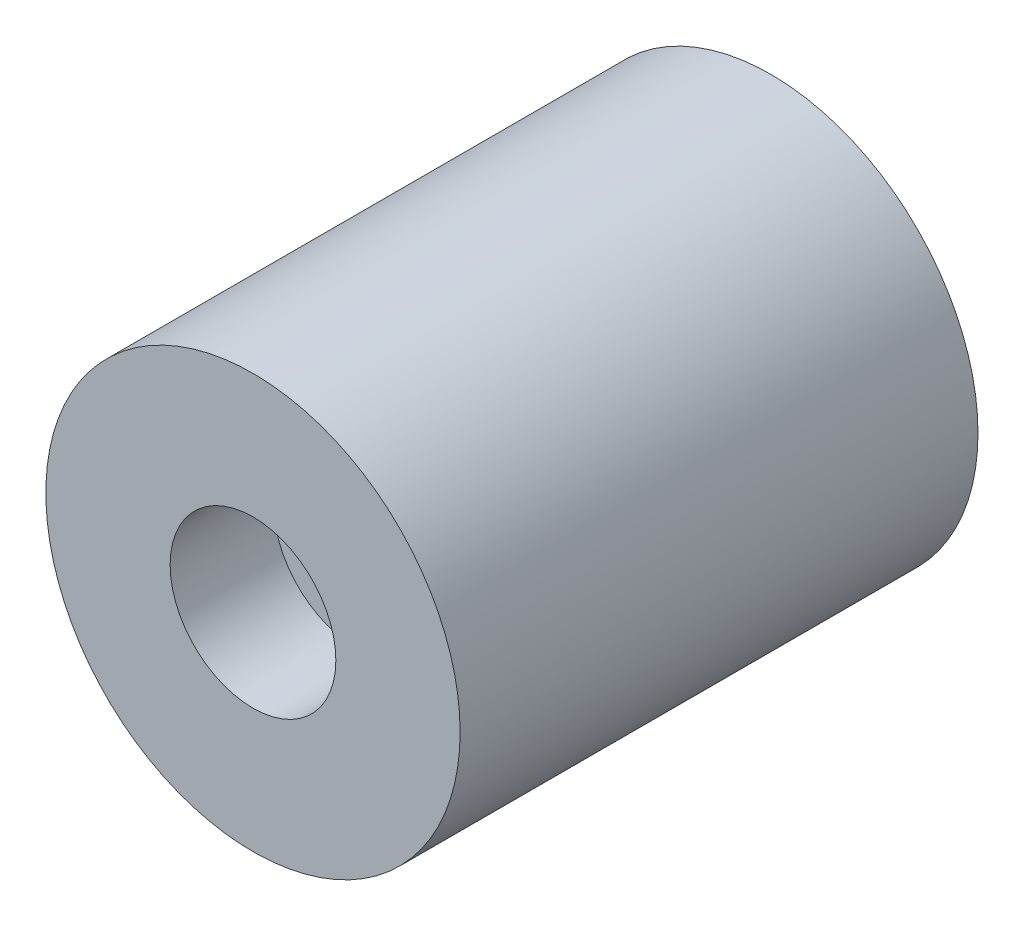
SolidWorks part; units mm, degrees
material "Chrome Stainless Steel"
ref_plane "Front Plane" through (0, 0, 0) normal (0, 0, 1) x (1, 0, 0)
ref_plane "Top Plane" through (0, 0, 0) normal (0, 1, 0) x (1, 0, 0)
ref_plane "Right Plane" through (0, 0, 0) normal (1, 0, 0) x (0, 0, -1)
sketch "Sketch1" plane through (0, 0, 0) normal (0, 0, 1) x (1, 0, 0)
  circle A0 centre (0, 0) radius 4
  circle A1 centre (0, 0) radius 10
  dimension "D1" = 8
  dimension "D2" = 20
extrude "Boss-Extrude1" add sketch "Sketch1" along normal blind 7.5 and the other way blind 7.5 contours A1 A0 | A0 region at (0, 0, 0) region at (-9.7172, 0, 0)
extrude "Boss-Extrude2" add sketch "Sketch1<2>" along normal blind 12.5 and the other way blind 12.5
sketch "Sketch1<2>" plane through (0, 0, 0) normal (0, 0, 1) x (1, 0, 0) same geometry as "Sketch1"
